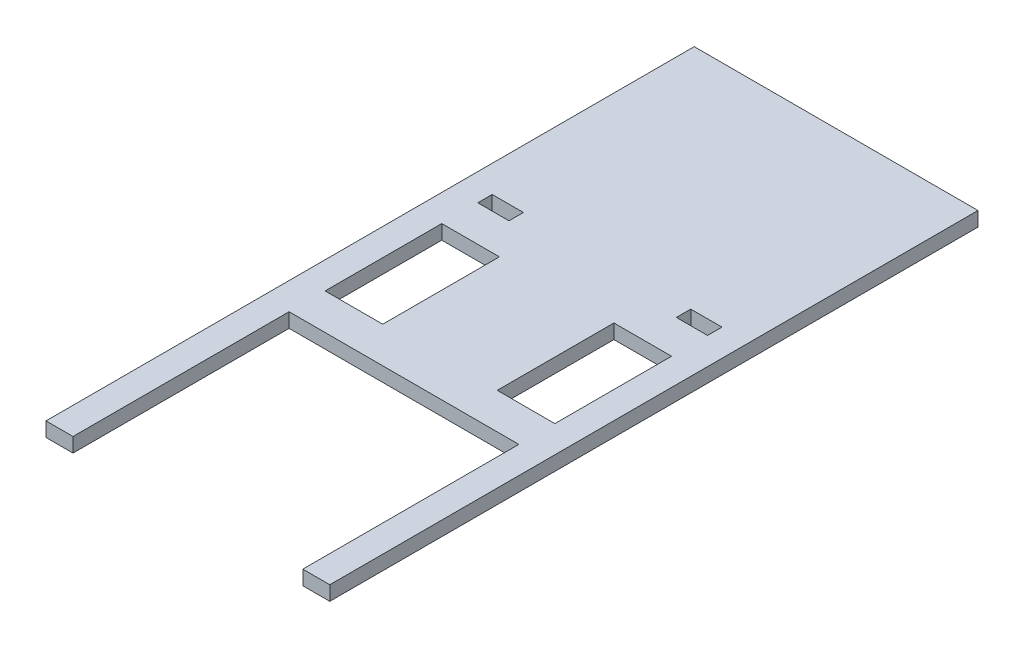
SolidWorks part; units mm, degrees
ref_plane "Front Plane" through (0, 0, 0) normal (0, 0, 1) x (1, 0, 0)
ref_plane "Top Plane" through (0, 0, 0) normal (0, 1, 0) x (1, 0, 0)
ref_plane "Right Plane" through (0, 0, 0) normal (1, 0, 0) x (0, 0, -1)
sketch "Sketch1" plane through (0, 0, 0) normal (0, 1, 0) x (1, 0, 0)
  line L1 (-50.038, 114.3) -> (50.038, 114.3)
  line L2 (-50.038, 114.3) -> (-50.038, -114.3)
  line L3 (-50.038, -114.3) -> (50.038, -114.3)
  line L4 (50.038, 114.3) -> (50.038, -114.3)
  line L5 (-50.038, 114.3) -> (50.038, -114.3) construction
  line L6 (-50.038, -114.3) -> (50.038, 114.3) construction
  point P0 (0, 0)
  dimension "D1" = 100.076
  dimension "D2" = 228.6
extrude "Boss-Extrude1" add sketch "Sketch1" along normal blind 5.08
sketch "Sketch2" plane through (0, 5.08, 0) normal (0, 1, 0) x (1, 0, 0)
  line L0 (-50.038, -114.3) -> (50.038, -114.3) construction
  line L1 (-40.513, -38.1) -> (40.513, -38.1)
  line L2 (-40.513, -38.1) -> (-40.513, -114.3)
  line L3 (-40.513, -114.3) -> (40.513, -114.3)
  line L4 (40.513, -38.1) -> (40.513, -114.3)
  line L5 (-50.038, 114.3) -> (-50.038, -114.3) construction
  line L6 (50.038, -114.3) -> (50.038, 114.3) construction
  dimension "D1" = 9.525
  dimension "D2" = 9.525
  dimension "D3" = 76.2
extrude "Cut-Extrude1" cut sketch "Sketch2" against normal blind 5.08
sketch "Sketch3" plane through (0, 5.08, 0) normal (0, 1, 0) x (1, 0, 0)
  line L0 (40.513, -38.1) -> (-40.513, -38.1) construction
  line L1 (-40.513, 15.748) -> (-20.193, 15.748)
  line L2 (-40.513, 15.748) -> (-40.513, -25.4)
  line L3 (-40.513, -25.4) -> (-20.193, -25.4)
  line L4 (-20.193, 15.748) -> (-20.193, -25.4)
  line L5 (-50.038, 114.3) -> (-50.038, -114.3) construction
  line L6 (0, 44.3201) -> (0, -22.352) construction
  line L7 (-40.513, 33.528) -> (-29.5148, 33.528)
  line L8 (-40.513, 33.528) -> (-40.513, 28.448)
  line L9 (-40.513, 28.448) -> (-29.5148, 28.448)
  line L10 (-29.5148, 33.528) -> (-29.5148, 28.448)
  line L11 (20.193, 15.748) -> (20.193, -25.4)
  line L12 (40.513, -25.4) -> (20.193, -25.4)
  line L13 (40.513, 15.748) -> (40.513, -25.4)
  line L14 (40.513, 15.748) -> (20.193, 15.748)
  line L15 (29.5148, 33.528) -> (29.5148, 28.448)
  line L16 (40.513, 28.448) -> (29.5148, 28.448)
  line L17 (40.513, 33.528) -> (40.513, 28.448)
  line L18 (40.513, 33.528) -> (29.5148, 33.528)
  dimension "D1" = 20.32
  dimension "D2" = 41.148
  dimension "D3" = 12.7
  dimension "D4" = 9.525
  dimension "D5" = 10.9982
  dimension "D6" = 5.08
  dimension "D7" = 9.525
  dimension "D8" = 12.7
extrude "Cut-Extrude2" cut sketch "Sketch3" against normal blind 5.08
